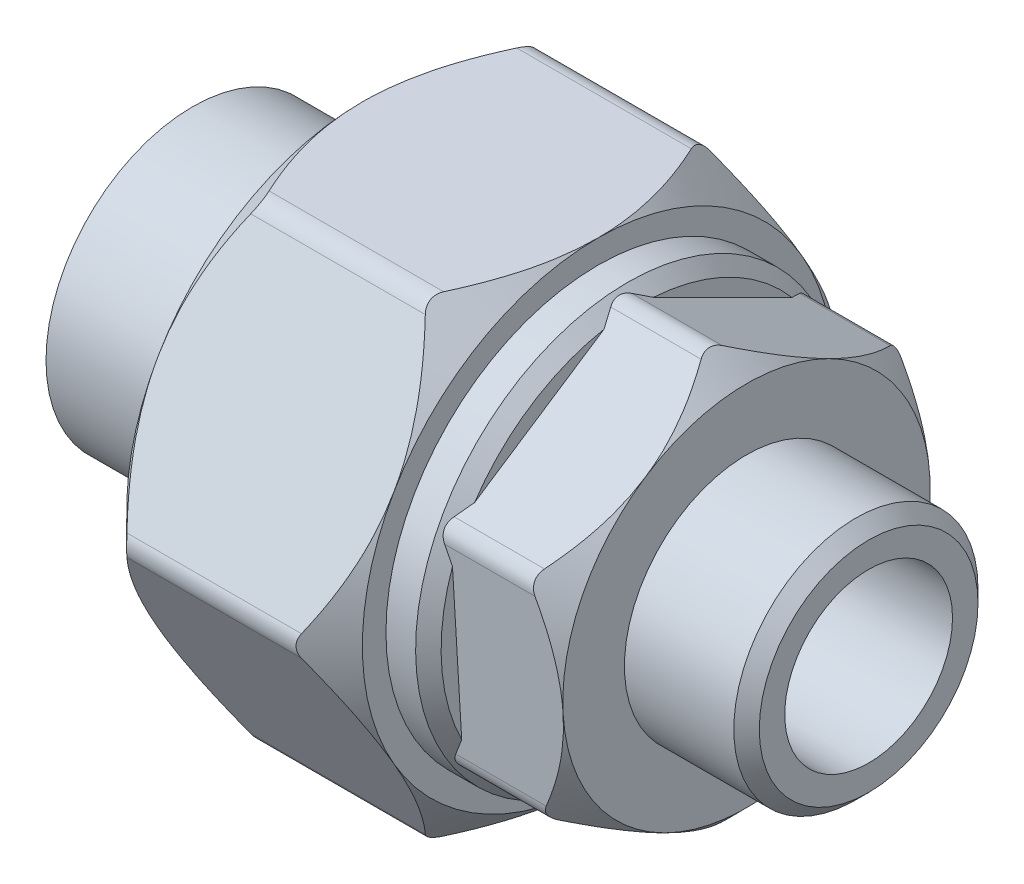
SolidWorks part; units mm, degrees
material "PE Высокой плотности"
ref_plane "Front" through (0, 0, 0) normal (0, 0, 1) x (1, 0, 0)
ref_plane "Top" through (0, 0, 0) normal (0, 1, 0) x (1, 0, 0)
ref_plane "Right" through (0, 0, 0) normal (1, 0, 0) x (0, 0, -1)
sketch "Эскиз1" plane through (0, 0, 0) normal (1, 0, 0) x (0, 0, -1)
  circle A0 centre (0, 0) radius 10
  dimension "d" = 20
extrude "Вытянуть-Тонкостенный1" add sketch "Эскиз1" along normal blind 13.3333 thin thin type one direction wall 1.5
sketch "Эскиз2" plane through (13.3333, 0, 0) normal (1, 0, 0) x (0, 0, -1)
  line L0 (50, 0) -> (-50, 0) construction
  line L1 (21.362, 0) -> (10.681, 18.5)
  line L2 (10.681, 18.5) -> (-10.681, 18.5)
  line L3 (-10.681, 18.5) -> (-21.362, 0)
  line L4 (-21.362, 0) -> (-10.681, -18.5)
  line L5 (-10.681, -18.5) -> (10.681, -18.5)
  line L6 (10.681, -18.5) -> (21.362, 0)
  circle A1 centre (0, 0) radius 18.5 construction
  dimension "D2" = 37
extrude "Бобышка-Вытянуть2" add sketch "Эскиз2" along normal blind 18.5
sketch "Эскиз8" plane through (13.3333, 0, 0) normal (-1, 0, 0) x (0, 0, 1)
  circle A0 centre (0, 0) radius 18.5 construction
  circle A1 centre (0, 0) radius 18.5
extrude "Вырез-Вытянуть4" cut sketch "Эскиз8" against normal blind 10 draft 45 flip side to cut
sketch "Эскиз9" plane through (31.8333, 0, 0) normal (1, 0, 0) x (0, 0, -1)
  circle A0 centre (0, 0) radius 18.5 construction
  circle A1 centre (0, 0) radius 18.5
extrude "Вырез-Вытянуть5" cut sketch "Эскиз9" against normal blind 10 draft 45 flip side to cut
sketch "Эскиз10" plane through (31.8333, 0, 0) normal (1, 0, 0) x (0, 0, -1)
  circle A0 centre (0, 0) radius 16.65
  dimension "R1" = 33.3
extrude "Бобышка-Вытянуть3" add sketch "Эскиз10" along normal blind 3.33
sketch "Эскиз11" plane through (35.1633, 0, 0) normal (1, 0, 0) x (0, 0, -1)
  line L1 (0.9915, -16.6205) -> (14.8895, -7.4516)
  line L2 (14.8895, -7.4516) -> (13.898, 9.1689)
  line L3 (13.898, 9.1689) -> (-0.9915, 16.6205)
  line L4 (-0.9915, 16.6205) -> (-14.8895, 7.4516)
  line L5 (-14.8895, 7.4516) -> (-13.898, -9.1689)
  line L6 (-13.898, -9.1689) -> (0.9915, -16.6205)
  circle A0 centre (0, 0) radius 14.4193 construction
  circle A1 centre (0, 0) radius 16.65 construction
  circle A2 centre (0, 0) radius 16.65 construction
extrude "Бобышка-Вытянуть4" add sketch "Эскиз11" along normal blind 8.325
sketch "Эскиз12" plane through (43.4883, 0, 0) normal (1, 0, 0) x (0, 0, -1)
  circle A0 centre (0, 0) radius 14.4193 construction
  circle A1 centre (0, 0) radius 14.4193
extrude "Вырез-Вытянуть6" cut sketch "Эскиз12" against normal blind 8.325 draft 45 flip side to cut
fillet "Скругление1" radius 1.665 12 edges at (22.5833, 18.5, -10.681) (22.5833, 0, -21.362) (22.5833, -18.5, -10.681) (22.5833, -18.5, 10.681) (22.5833, 18.5, 10.681) (22.5833, 0, 21.362) (38.2105, -16.6205, -0.9915) (38.2105, -9.1689, 13.898) (38.2105, 7.4516, 14.8895) (38.2105, -7.4516, -14.8895) (38.2105, 9.1689, -13.898) (38.2105, 16.6205, 0.9915)
chamfer "Фаска1" distance 1 angle 45 6 edges at (35.1633, 14.8895, -7.4516) (35.1633, 13.898, 9.1689) (35.1633, -0.9915, 16.6205) (35.1633, -14.8895, 7.4516) (35.1633, -13.898, -9.1689) (35.1633, 0.9915, -16.6205)
sketch "Эскиз13" plane through (43.4883, 0, 0) normal (1, 0, 0) x (0, 0, -1)
  circle A0 centre (0, 0) radius 9.585
  dimension "R" = 19.17
sketch3d "Трехмерный эскиз1"
  line L0 (0, 0, 0) -> (43.4883, 0, 0) construction
other "Точка соединения1" parameters "Диаметр"=20, "StubLength"=0
ref_axis "Ось1" through (-10, 0, 0) along (1, 0, 0)
extrude "Бобышка-Вытянуть5" add sketch "Эскиз13" along normal blind 9.585
chamfer "Фаска2" distance 1 angle 45 1 edges at (53.0733, 0, -9.585)
sketch "Эскиз14" plane through (53.0733, 0, 0) normal (1, 0, 0) x (0, 0, -1)
  circle A4 centre (0, 0) radius 6.585
  circle A5 centre (0, 0) radius 6.585
  dimension "D1" = 3
extrude "Вырез-Вытянуть7" cut sketch "Эскиз14" against normal through all
equation "\"D1@Бобышка-Вытянуть5\"=\"R@Эскиз13\" / 2"
